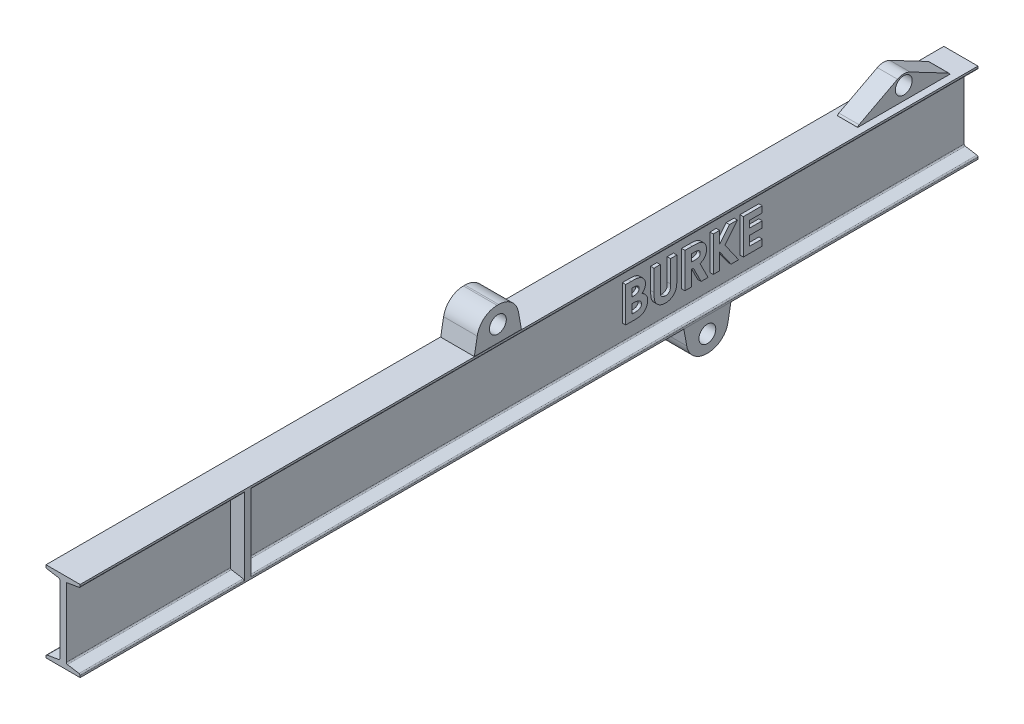
SolidWorks part; units mm, degrees
material "Custom Plastic"
ref_plane "Front Plane" through (0, 0, 0) normal (0, 0, 1) x (1, 0, 0)
ref_plane "Top Plane" through (0, 0, 0) normal (0, 1, 0) x (1, 0, 0)
ref_plane "Right Plane" through (0, 0, 0) normal (1, 0, 0) x (0, 0, -1)
sketch "Sketch1" plane through (0, 0, 0) normal (0, 0, 1) x (1, 0, 0)
  line L0 (-3.0125, -7.041) -> (-0.8121, -6.6727)
  line L1 (-3.2245, 7.62) -> (3.2245, 7.62) construction
  line L2 (-3.2245, 7.62) -> (-3.2245, -7.62) construction
  line L3 (-3.2245, -7.62) -> (3.2245, -7.62) construction
  line L4 (3.2245, 7.62) -> (3.2245, -7.62) construction
  line L5 (-3.2245, 7.62) -> (3.2245, -7.62) construction
  line L6 (-3.2245, -7.62) -> (3.2245, 7.62) construction
  line L7 (-3.2245, 7.62) -> (-0.2718, 7.62)
  line L8 (-3.2245, 7.62) -> (-3.2245, 7.2915)
  line L9 (-3.0125, 7.041) -> (-0.8121, 6.6727)
  line L10 (3.2245, 7.62) -> (3.2245, 7.2915)
  line L11 (-3.2245, -7.62) -> (-0.2718, -7.62)
  line L12 (-3.2245, -7.62) -> (-3.2245, -7.2915)
  line L13 (3.0125, 7.041) -> (0.6, 6.6372)
  line L14 (3.2245, -7.62) -> (3.2245, -7.2915)
  line L15 (-0.2718, 7.62) -> (0.2718, 7.62)
  line L16 (-0.6, 6.4222) -> (-0.6, -6.4222)
  line L17 (-0.2718, -7.62) -> (0.2718, -7.62)
  line L18 (0.6, 6.6372) -> (0.6, -6.4222)
  line L19 (3.0125, -7.041) -> (0.8121, -6.6727)
  line L20 (0.2718, 7.62) -> (3.2245, 7.62)
  line L21 (0.2718, -7.62) -> (3.2245, -7.62)
  arc A0 (-0.6, -6.4222) -> (-0.8121, -6.6727) centre (-0.854, -6.4222) cw
  arc A1 (-3.2245, -7.2915) -> (-3.0125, -7.041) centre (-2.9705, -7.2915) cw
  arc A2 (3.2245, -7.2915) -> (3.0125, -7.041) centre (2.9705, -7.2915) ccw
  arc A3 (0.8121, -6.6727) -> (0.6, -6.4222) centre (0.854, -6.4222) cw
  arc A4 (3.2245, 7.2915) -> (3.0125, 7.041) centre (2.9705, 7.2915) cw
  arc A5 (-3.2245, 7.2915) -> (-3.0125, 7.041) centre (-2.9705, 7.2915) ccw
  arc A6 (-0.6, 6.4222) -> (-0.8121, 6.6727) centre (-0.854, 6.4222) ccw
  point P0 (0, 0)
  point P20 (-0.6, -6.6372)
  point P23 (-3.2245, -7.0764)
  point P26 (3.2245, -7.0764)
  point P29 (0.6, -6.6372)
  point P32 (3.2245, 7.0764)
  point P35 (-3.2245, 7.0764)
  point P38 (-0.6, 6.6372)
  dimension "D11" = 0.254
  dimension "D1" = 15.24
  dimension "D2" = 6.4491
  dimension "D3" = 0.5436
  dimension "D4" = 0.5436
  dimension "D5" = 1.2
  dimension "D6" = 0.6
  dimension "D7" = 9.5
  dimension "D8" = 9.5
  dimension "D9" = 9.5
  dimension "D10" = 9.5
extrude "Boss-Extrude1" add sketch "Sketch1" along normal mid plane 169.545
sketch "Sketch2" plane through (0, 0, 0) normal (1, 0, 0) x (0, 0, -1)
  line L0 (72.0725, 7.2915) -> (72.0725, 12.3715) construction
  line L1 (-84.7725, 7.62) -> (84.7725, 7.62) construction
  line L2 (-84.7725, 7.2915) -> (84.7725, 7.2915) construction
  line L3 (70.8922, 11.7521) -> (63.6322, 7.9422)
  line L4 (63.3602, 7.4924) -> (63.3602, 7.2915)
  line L5 (73.2528, 11.7521) -> (80.5128, 7.9422)
  line L6 (80.7848, 7.2915) -> (63.3602, 7.2915)
  line L7 (80.7848, 7.4924) -> (80.7848, 7.2915)
  circle A0 centre (72.0725, 10.16) radius 1.5875
  arc A1 (80.7848, 7.4924) -> (80.5128, 7.9422) centre (80.2768, 7.4924) ccw
  arc A2 (63.3602, 7.4924) -> (63.6322, 7.9422) centre (63.8682, 7.4924) cw
  arc A3 (73.2528, 11.7521) -> (70.8922, 11.7521) centre (72.0725, 9.503) ccw
  point P13 (80.7848, 7.7995)
  point P18 (63.3602, 7.7995)
  dimension "D1" = 2.54
  dimension "D2" = 3.175
  dimension "D5" = 5.08
  dimension "D7" = 0.508
  dimension "D8" = 2.54
  dimension "D3" = 12.7
  dimension "D4" = 17.4245
  dimension "D6" = 0.508
extrude "Boss-Extrude2" add sketch "Sketch2" along normal mid plane 3.81
sketch "Sketch3" plane through (0, 0, 0) normal (1, 0, 0) x (0, 0, -1)
  line L0 (84.7725, -6.4222) -> (84.7725, 6.6372) construction
  line L1 (-84.7725, -7.2915) -> (84.7725, -7.2915) construction
  line L2 (29.2735, -7.62) -> (38.1635, -7.62)
  line L3 (-84.7725, -7.62) -> (84.7725, -7.62) construction
  line L4 (38.1635, -7.62) -> (37.6211, -10.6963)
  line L5 (33.869, -13.8447) -> (33.568, -13.8447)
  line L6 (29.8159, -10.6963) -> (29.2735, -7.62)
  circle A0 centre (33.7185, -10.6697) radius 1.5875
  circle A1 centre (33.7185, -10.6697) radius 3.175 construction
  arc A2 (37.6211, -10.6963) -> (33.869, -13.8447) centre (33.869, -10.0347) cw
  arc A3 (33.568, -13.8447) -> (29.8159, -10.6963) centre (33.568, -10.0347) cw
  point P17 (33.8649, -13.8447)
  point P18 (33.5721, -13.8447)
  point P19 (33.8649, -13.8413)
  point P20 (0, 0)
  dimension "D3" = 3.175
  dimension "D9" = 3.81
  dimension "D4" = 6.35
  dimension "D1" = 51.054
  dimension "D2" = 3.3782
  dimension "D7" = 8.89
  dimension "D8" = 4.445
  dimension "D5" = 80
  dimension "D6" = 80
extrude "Boss-Extrude3" add sketch "Sketch3" along normal mid plane 6.35
sketch "Sketch6" plane through (0.6, 0, 0) normal (1, 0, 0) x (0, 0, -1)
  line L0 (-84.7725, -6.4222) -> (-84.7725, 6.6372) construction
  line L1 (-53.7845, 7.2915) -> (-52.5145, 7.2915)
  line L2 (-53.7845, 7.2915) -> (-53.7845, -7.2915)
  line L3 (-53.7845, -7.2915) -> (-52.5145, -7.2915)
  line L4 (-52.5145, 7.2915) -> (-52.5145, -7.2915)
  line L5 (-84.7725, 7.2915) -> (84.7725, 7.2915) construction
  line L6 (-84.7725, -7.2915) -> (84.7725, -7.2915) construction
  dimension "D1" = 30.988
  dimension "D2" = 1.27
extrude "Boss-Extrude5" add sketch "Sketch6" along normal up to surface (2.6245 mm away) up to face at (3.2245, 7.4557, 0)
extrude "Boss-Extrude6" add sketch "Sketch6<2>" against normal up to surface (3.8245 mm away) up to face at (-3.2245, 7.4557, 0)
sketch "Sketch6<2>" plane through (0.6, 0, 0) normal (1, 0, 0) x (0, 0, -1) same geometry as "Sketch6"
sketch "Sketch5" [suppressed] plane through (0, 0, 0) normal (1, 0, 0) x (0, 0, -1)
  line L0 (33.7185, -10.6697) -> (33.7185, 0) construction
  line L1 (33.7185, 0) -> (13.9383, 0) construction
  dimension "D1" = 19.7802
ref_axis "Axis1" [suppressed] through (0, 0, -13.9383) along (1, 0, 0)
pattern_circular "CirPattern1" count 2 over 360 about axis through (0, 0, -13.9383) along (1, 0, 0) of "Boss-Extrude3"
sketch "Sketch7" plane through (0.6, 0, 0) normal (1, 0, 0) x (0, 0, -1)
  text T0 "BURKE" font "Century Gothic" height in points 25
extrude "Boss-Extrude7" add sketch "Sketch7" along normal blind 0.635
sketch "Sketch8" plane through (-0.6, 0, 0) normal (-1, 0, 0) x (0, 0, 1)
  text T0 "BURKE" font "Century Gothic" height in points 25
extrude "Boss-Extrude8" add sketch "Sketch8" along normal blind 0.635
equation "\"D8@Sketch1\"=\"D7@Sketch1\""
equation "\"D9@Sketch1\"=\"D7@Sketch1\""
equation "\"D10@Sketch1\"=\"D7@Sketch1\""
equation "\"D8@Sketch3\"=\"D7@Sketch3\"/2"
equation "\"D6@Sketch3\"=\"D5@Sketch3\""
equation "\"D6@Sketch1\"=\"D5@Sketch1\"/2"
